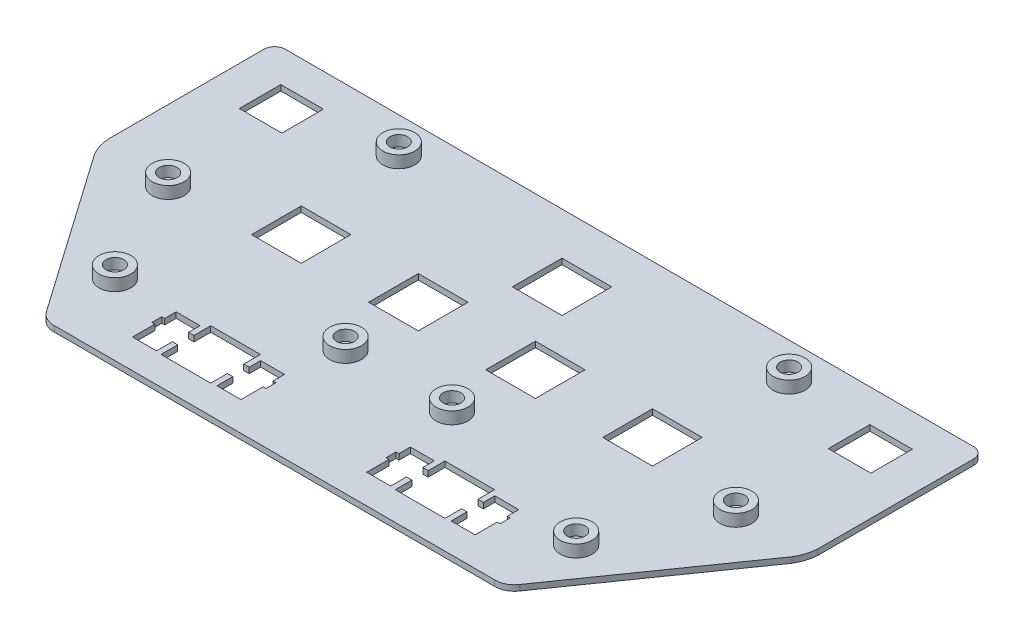
SolidWorks part; units mm, degrees
ref_plane "前视基准面" through (0, 0, 0) normal (0, 0, 1) x (1, 0, 0)
ref_plane "上视基准面" through (0, 0, 0) normal (0, 1, 0) x (1, 0, 0)
ref_plane "右视基准面" through (0, 0, 0) normal (1, 0, 0) x (0, 0, -1)
other "Configuration Table"
sketch "草图1" plane through (0, 0, 0) normal (0, 1, 0) x (1, 0, 0)
  line L0 (0, 0) -> (200, 0) construction
  line L1 (200, 0) -> (200, -100) construction
  line L2 (200, -100) -> (0, -100) construction
  line L3 (0, -100) -> (0, 0) construction
  line L4 (0, -100) -> (35, -100) construction
  line L5 (200, -100) -> (165, -100) construction
  line L6 (0, -50) -> (35, -100) construction
  line L7 (165, -100) -> (200, -50) construction
  line L8 (200, -50) -> (200, -47) construction
  line L9 (0, -50) -> (0, -47) construction
  line L10 (35, -100) -> (38, -100) construction
  line L11 (165, -100) -> (162, -100) construction
  line L12 (0, 0) -> (0, -3) construction
  line L13 (0, -3) -> (3, -3) construction
  line L14 (200, 0) -> (200, -3) construction
  line L15 (200, -3) -> (197, -3) construction
  line L16 (197, 0) -> (3, 0)
  line L17 (0, -3) -> (0, -47)
  line L18 (1.7204, -52.4577) -> (33.2796, -97.5423)
  line L19 (38, -100) -> (162, -100)
  line L20 (166.7204, -97.5423) -> (198.2796, -52.4577)
  line L21 (200, -47) -> (200, -3)
  line L22 (0, 0) -> (0, -5) construction
  line L23 (0, -5) -> (5, -5) construction
  line L24 (200, 0) -> (200, -5) construction
  line L25 (200, -5) -> (195, -5) construction
  line L26 (100, 0) -> (100, -12) construction
  line L35 (107, -12) -> (93, -12) construction
  line L36 (93, -26) -> (90.5, -26) construction
  line L37 (93, -12) -> (107, -12)
  line L38 (93, -12) -> (93, -26)
  line L39 (93, -26) -> (107, -26)
  line L40 (107, -12) -> (107, -26)
  line L41 (90.5, -26) -> (90.5, -36) construction
  line L42 (107, -26) -> (109.5, -26) construction
  line L43 (109.5, -26) -> (109.5, -36) construction
  line L44 (76.5, -36) -> (57.5, -36) construction
  line L45 (90.5, -36) -> (76.5, -36)
  line L46 (90.5, -36) -> (90.5, -50)
  line L47 (90.5, -50) -> (76.5, -50)
  line L48 (76.5, -36) -> (76.5, -50)
  line L49 (109.5, -36) -> (123.5, -36)
  line L50 (109.5, -36) -> (109.5, -50)
  line L51 (109.5, -50) -> (123.5, -50)
  line L52 (123.5, -36) -> (123.5, -50)
  line L53 (123.5, -36) -> (142.5, -36) construction
  line L54 (57.5, -36) -> (43.5, -36)
  line L55 (57.5, -36) -> (57.5, -50)
  line L56 (57.5, -50) -> (43.5, -50)
  line L57 (43.5, -36) -> (43.5, -50)
  line L58 (67, -36) -> (67, -78) construction
  line L59 (142.5, -36) -> (156.5, -36)
  line L60 (142.5, -36) -> (142.5, -50)
  line L61 (142.5, -50) -> (156.5, -50)
  line L62 (156.5, -36) -> (156.5, -50)
  line L63 (133, -36) -> (133, -78) construction
  line L64 (60, -78) -> (74, -78) construction
  line L65 (140, -78) -> (126, -78) construction
  line L66 (5, -5) -> (5, -15.1) construction
  line L67 (60, -78) -> (74, -78)
  line L69 (60, -92) -> (74, -92)
  line L71 (140, -78) -> (126, -78)
  line L73 (140, -92) -> (126, -92)
  line L75 (5, -15.1) -> (11, -15.1) construction
  line L76 (195, -5) -> (195, -15.1) construction
  line L77 (11, -20.95) -> (23, -20.95)
  line L78 (11, -20.95) -> (11, -9.25)
  line L79 (11, -9.25) -> (23, -9.25)
  line L80 (23, -20.95) -> (23, -9.25)
  line L81 (195, -15.1) -> (189, -15.1) construction
  line L82 (74, -78) -> (74, -82.7)
  line L83 (189, -20.95) -> (177, -20.95)
  line L84 (189, -20.95) -> (189, -9.25)
  line L85 (189, -9.25) -> (177, -9.25)
  line L86 (177, -20.95) -> (177, -9.25)
  line L87 (74, -92) -> (74, -87.3)
  line L88 (74, -82.7) -> (75.525, -82.7)
  line L89 (74, -87.3) -> (75.525, -87.3)
  line L90 (75.525, -82.7) -> (75.525, -79.47)
  line L91 (75.525, -87.3) -> (75.525, -91.77)
  line L92 (75.525, -79.47) -> (82.275, -79.47)
  line L93 (82.275, -79.47) -> (82.275, -82.7)
  line L94 (82.275, -82.7) -> (83.1, -82.7)
  line L95 (83.1, -82.7) -> (83.1, -85.5)
  line L96 (83.1, -85.5) -> (82.275, -85.5)
  line L97 (82.275, -85.5) -> (82.275, -91.77)
  line L98 (82.275, -91.77) -> (75.525, -91.77)
  line L101 (60, -78) -> (60, -82.7)
  line L102 (60, -92) -> (60, -87.3)
  line L103 (60, -82.7) -> (58.475, -82.7)
  line L104 (58.475, -82.7) -> (58.475, -79.47)
  line L105 (58.475, -79.47) -> (51.725, -79.47)
  line L106 (51.725, -79.47) -> (51.725, -82.7)
  line L107 (51.725, -82.7) -> (50.9, -82.7)
  line L108 (50.9, -82.7) -> (50.9, -85.5)
  line L109 (50.9, -85.5) -> (51.725, -85.5)
  line L110 (51.725, -85.5) -> (51.725, -91.77)
  line L111 (51.725, -91.77) -> (58.475, -91.77)
  line L112 (58.475, -91.77) -> (58.475, -87.3)
  line L113 (58.475, -87.3) -> (60, -87.3)
  line L114 (140, -78) -> (140, -82.7)
  line L115 (140, -82.7) -> (141.525, -82.7)
  line L116 (141.525, -82.7) -> (141.525, -79.47)
  line L117 (141.525, -79.47) -> (148.275, -79.47)
  line L118 (148.275, -79.47) -> (148.275, -82.7)
  line L119 (148.275, -82.7) -> (149.1, -82.7)
  line L120 (149.1, -82.7) -> (149.1, -85.5)
  line L121 (149.1, -85.5) -> (148.275, -85.5)
  line L122 (148.275, -85.5) -> (148.275, -91.77)
  line L123 (148.275, -91.77) -> (141.525, -91.77)
  line L124 (141.525, -91.77) -> (141.525, -87.3)
  line L125 (141.525, -87.3) -> (140, -87.3)
  line L126 (140, -87.3) -> (140, -92)
  line L127 (126, -78) -> (126, -82.7)
  line L128 (126, -82.7) -> (124.475, -82.7)
  line L129 (124.475, -82.7) -> (124.475, -79.47)
  line L130 (124.475, -79.47) -> (117.725, -79.47)
  line L131 (117.725, -79.47) -> (117.725, -82.7)
  line L132 (117.725, -82.7) -> (116.9, -82.7)
  line L133 (116.9, -82.7) -> (116.9, -85.5)
  line L134 (116.9, -85.5) -> (117.725, -85.5)
  line L135 (117.725, -85.5) -> (117.725, -91.77)
  line L136 (117.725, -91.77) -> (124.475, -91.77)
  line L137 (124.475, -91.77) -> (124.475, -87.3)
  line L138 (124.475, -87.3) -> (126, -87.3)
  line L139 (126, -87.3) -> (126, -92)
  arc A0 (200, -47) -> (198.2796, -52.4577) centre (200, -50) ccw construction
  arc A1 (200, -47) -> (198.2796, -52.4577) centre (197.1388, -49.0981) ccw construction
  arc A2 (200, -47) -> (198.2796, -52.4577) centre (193.7549, -48.0314) ccw construction
  arc A3 (200, -47) -> (198.2796, -52.4577) centre (187.718, -46.1284) cw
  arc A4 (0, -47) -> (1.7204, -52.4577) centre (0, -50) cw construction
  arc A5 (0, -47) -> (1.7204, -52.4577) centre (2.8612, -49.0981) cw construction
  arc A6 (0, -47) -> (1.7204, -52.4577) centre (6.2451, -48.0314) cw construction
  arc A7 (0, -47) -> (1.7204, -52.4577) centre (12.282, -46.1284) ccw
  arc A8 (38, -100) -> (33.2796, -97.5423) centre (35, -100) ccw construction
  arc A9 (38, -100) -> (33.2796, -97.5423) centre (36.3854, -97.3391) ccw construction
  arc A10 (33.2796, -97.5423) -> (38, -100) centre (37.8228, -94.5784) ccw
  arc A11 (162, -100) -> (166.7204, -97.5423) centre (165, -100) cw construction
  arc A12 (162, -100) -> (166.7204, -97.5423) centre (163.6146, -97.3391) cw construction
  arc A13 (162, -100) -> (166.7204, -97.5423) centre (162.1772, -94.5784) ccw
  arc A14 (0, -3) -> (3, 0) centre (3, -3) cw
  arc A15 (200, -3) -> (197, 0) centre (197, -3) ccw
  point P48 (100, -12)
  point P75 (67, -78)
  point P78 (133, -78)
  dimension "D12" = 3
  dimension "D10" = 3
  dimension "D1" = 200
  dimension "D2" = 100
  dimension "D3" = 35
  dimension "D4" = 35
  dimension "D5" = 3
  dimension "D6" = 3
  dimension "D7" = 3
  dimension "D8" = 3
  dimension "D9" = 44
  dimension "D11" = 44
  dimension "D13" = 5
  dimension "D14" = 5
  dimension "D15" = 5
  dimension "D16" = 5
  dimension "D17" = 10.1
  dimension "D18" = 6
  dimension "D19" = 10.1
  dimension "D20" = 6
  dimension "D21" = 12
  dimension "D22" = 14
  dimension "D23" = 14
  dimension "D24" = 2.5
  dimension "D25" = 10
  dimension "D26" = 2.5
  dimension "D27" = 10
  dimension "D28" = 14
  dimension "D29" = 14
  dimension "D30" = 14
  dimension "D31" = 14
  dimension "D32" = 19
  dimension "D33" = 14
  dimension "D34" = 14
  dimension "D35" = 19
  dimension "D36" = 14
  dimension "D37" = 14
  dimension "D38" = 42
  dimension "D39" = 42
  dimension "D40" = 14
  dimension "D41" = 14
  dimension "D42" = 4.7
  dimension "D43" = 14
  dimension "D44" = 12
  dimension "D45" = 11.7
  dimension "D46" = 4.7
  dimension "D47" = 4.7
  dimension "D48" = 11.7
  dimension "D49" = 12
  dimension "D50" = 4.7
  dimension "D51" = 4.6
  dimension "D52" = 4.6
  dimension "D53" = 1.525
  dimension "D54" = 1.525
  dimension "D55" = 1.525
  dimension "D56" = 3.23
  dimension "D57" = 3.23
  dimension "D58" = 6.75
  dimension "D59" = 6.75
  dimension "D60" = 3.23
  dimension "D61" = 0.825
  dimension "D62" = 2.8
  dimension "D63" = 0.825
  dimension "D64" = 6.27
  dimension "D65" = 3.23
  dimension "D66" = 0.825
  dimension "D67" = 2.8
  dimension "D68" = 0.825
  dimension "D69" = 6.27
  dimension "D70" = 6.75
  dimension "D71" = 4.7
  dimension "D72" = 1.525
  dimension "D73" = 3.23
  dimension "D74" = 6.75
  dimension "D75" = 3.23
  dimension "D76" = 0.825
  dimension "D77" = 2.8
  dimension "D78" = 0.825
  dimension "D79" = 6.27
  dimension "D80" = 6.75
  dimension "D81" = 4.47
  dimension "D82" = 1.525
  dimension "D83" = 4.7
  dimension "D84" = 4.7
  dimension "D85" = 1.525
  dimension "D86" = 3.23
  dimension "D87" = 6.75
  dimension "D88" = 3.23
  dimension "D89" = 0.825
  dimension "D90" = 2.8
  dimension "D91" = 0.825
  dimension "D92" = 6.27
  dimension "D93" = 6.75
  dimension "D94" = 4.47
  dimension "D95" = 1.525
  dimension "D96" = 4.7
extrude "凸台-拉伸1" add sketch "草图1" along normal blind 1.6
sketch "草图2" plane through (0, 0, 0) normal (0, 1, 0) x (1, 0, 0)
  line L6 (0, 0) -> (0, -100) construction
  line L7 (0, 0) -> (200, 0) construction
  line L8 (0, -100) -> (200, -100) construction
  line L9 (200, -100) -> (200, 0) construction
  line L10 (0, -100) -> (35, -100) construction
  line L11 (200, -100) -> (165, -100) construction
  line L12 (200, -47) -> (200, -3)
  line L13 (197, 0) -> (3, 0)
  line L14 (0, -3) -> (0, -47)
  line L15 (1.7204, -52.4577) -> (33.2796, -97.5423)
  line L16 (38, -100) -> (162, -100)
  line L17 (166.7204, -97.5423) -> (198.2796, -52.4577)
  line L18 (200, -47) -> (200, -3) construction
  line L19 (197, 0) -> (3, 0) construction
  line L20 (0, -3) -> (0, -47) construction
  line L22 (38, -100) -> (162, -100) construction
  line L24 (35, -100) -> (0, -50) construction
  line L25 (165, -100) -> (200, -50) construction
  line L26 (0, -50) -> (20, -50) construction
  line L27 (45, 0) -> (45, -10) construction
  line L28 (200, 0) -> (155, 0) construction
  line L29 (155, 0) -> (155, -10) construction
  line L30 (200, -50) -> (180, -50) construction
  line L31 (165, -100) -> (165, -80) construction
  line L32 (35, -100) -> (35, -80) construction
  line L33 (35, -80) -> (35, -65) construction
  line L34 (35, -65) -> (85, -65) construction
  line L35 (165, -80) -> (165, -65) construction
  line L36 (165, -65) -> (115, -65) construction
  circle A6 centre (45, -10) radius 2.5
  circle A7 centre (155, -10) radius 2.5
  circle A8 centre (20, -50) radius 2.5
  circle A9 centre (35, -80) radius 2.5
  circle A10 centre (85, -65) radius 2.5
  circle A11 centre (180, -50) radius 2.5
  arc A12 (198.2796, -52.4577) -> (200, -47) centre (187.718, -46.1284) ccw
  arc A13 (200, -3) -> (197, 0) centre (197, -3) ccw
  arc A14 (3, 0) -> (0, -3) centre (3, -3) ccw
  arc A15 (0, -47) -> (1.7204, -52.4577) centre (12.282, -46.1284) ccw
  arc A16 (33.2796, -97.5423) -> (38, -100) centre (37.8228, -94.5784) ccw
  arc A17 (162, -100) -> (166.7204, -97.5423) centre (162.1772, -94.5784) ccw
  arc A18 (198.2796, -52.4577) -> (200, -47) centre (187.718, -46.1284) ccw construction
  arc A19 (200, -3) -> (197, 0) centre (197, -3) ccw construction
  arc A20 (3, 0) -> (0, -3) centre (3, -3) ccw construction
  arc A21 (0, -47) -> (1.7204, -52.4577) centre (12.282, -46.1284) ccw construction
  arc A22 (33.2796, -97.5423) -> (38, -100) centre (37.8228, -94.5784) ccw construction
  arc A23 (162, -100) -> (166.7204, -97.5423) centre (162.1772, -94.5784) ccw construction
  circle A24 centre (165, -80) radius 2.5
  circle A25 centre (115, -65) radius 2.5
  circle A26 centre (35, -80) radius 4.5
  circle A27 centre (20, -50) radius 4.5
  circle A28 centre (45, -10) radius 4.5
  circle A29 centre (85, -65) radius 4.5
  circle A30 centre (115, -65) radius 4.5
  circle A31 centre (165, -80) radius 4.5
  circle A32 centre (155, -10) radius 4.5
  circle A33 centre (180, -50) radius 4.5
  dimension "D16" = 5
  dimension "D17" = 5
  dimension "D18" = 5
  dimension "D19" = 5
  dimension "D20" = 5
  dimension "D21" = 5
  dimension "D22" = 5
  dimension "D23" = 5
  dimension "D2" = 35
  dimension "D3" = 200
  dimension "D4" = 35
  dimension "D5" = 45
  dimension "D6" = 10
  dimension "D7" = 45
  dimension "D8" = 10
  dimension "D9" = 20
  dimension "D10" = 20
  dimension "D11" = 20
  dimension "D12" = 20
  dimension "D13" = 15
  dimension "D14" = 50
  dimension "D15" = 50
  dimension "D1" = 0
  dimension "D24" = 2
extrude "凸台-拉伸2" add sketch "草图2" along normal blind 5
sketch "草图3" plane through (0, 0, 0) normal (0, 1, 0) x (1, 0, 0)
  circle A8 centre (180, -50) radius 2.5 construction
  circle A9 centre (165, -80) radius 2.5 construction
  circle A10 centre (115, -65) radius 2.5 construction
  circle A11 centre (155, -10) radius 2.5 construction
  circle A12 centre (45, -10) radius 2.5 construction
  circle A13 centre (20, -50) radius 2.5 construction
  circle A14 centre (35, -80) radius 2.5 construction
  circle A15 centre (85, -65) radius 2.5 construction
  circle A16 centre (180, -50) radius 2.5
  circle A17 centre (165, -80) radius 2.5
  circle A18 centre (115, -65) radius 2.5
  circle A19 centre (155, -10) radius 2.5
  circle A20 centre (45, -10) radius 2.5
  circle A21 centre (20, -50) radius 2.5
  circle A22 centre (35, -80) radius 2.5
  circle A23 centre (85, -65) radius 2.5
extrude "凸台-拉伸3" add sketch "草图3" along normal blind 2
